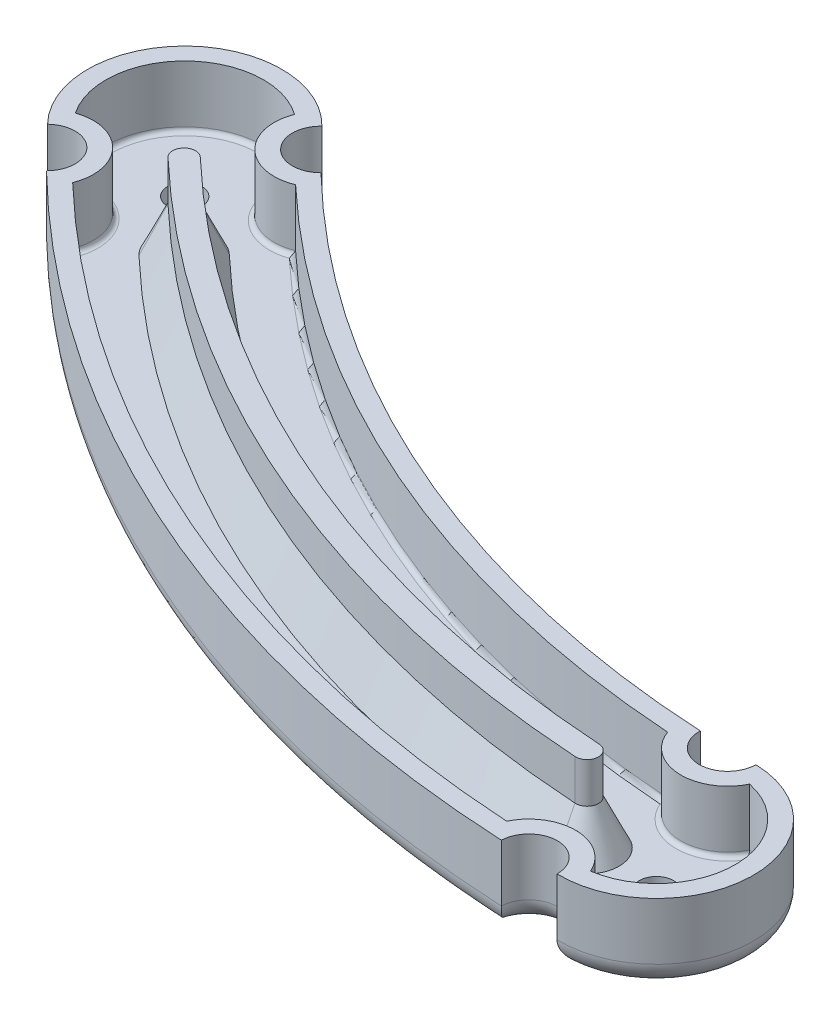
SolidWorks part; units mm, degrees
ref_plane "Front Plane" through (0, 0, 0) normal (0, 0, 1) x (1, 0, 0)
ref_plane "Top Plane" through (0, 0, 0) normal (0, 1, 0) x (1, 0, 0)
ref_plane "Right Plane" through (0, 0, 0) normal (1, 0, 0) x (0, 0, -1)
sketch "Sketch2" plane through (0, 0, 0) normal (0, 1, 0) x (1, 0, 0)
  line L0 (-71.3503, -82.2054) -> (-34958.9124, 35734.8019) construction
  line L1 (-70.1201, -59.1107) -> (-34995.8073, 35720.7213) construction
  line L2 (-39.7979, -107.5277) -> (49945.2079, -1331.9458) construction
  line L3 (31.7139, -92.3079) -> (50015.3873, -1369.9589) construction
  circle A0 centre (0, 0) radius 100 construction
  arc A1 (-0.2082, -108.4975) -> (0.2172, -91.5028) centre (0, -100) ccw
  arc A2 (-67.2386, -62.0626) -> (-79.4101, -73.9309) centre (-73.3212, -68) ccw
  arc A3 (-63.7464, -65.6403) -> (-4.7807, -91.375) centre (0, 0) ccw
  arc A4 (-75.9216, -77.5123) -> (-5.2063, -108.375) centre (0, 0) ccw
  arc A5 (-67.2386, -62.0626) -> (-63.7464, -65.6403) centre (-65.5159, -63.8743) ccw
  arc A6 (-75.9216, -77.5123) -> (-79.4101, -73.9309) centre (-77.6873, -75.7425) ccw
  arc A7 (-4.7807, -91.375) -> (0.2172, -91.5028) centre (-2.2826, -91.4715) ccw
  arc A8 (-0.2082, -108.4975) -> (-5.2063, -108.375) centre (-2.708, -108.4662) ccw
  dimension "D1" = 200
  dimension "D3" = 17
  dimension "D4" = 5
  dimension "D2" = 80
extrude "Boss-Extrude1" add sketch "Sketch2" along normal blind 7
fillet "Fillet1" radius 2 8 edges at (8.4973, 0, 100.2127) (-2.3465, 0, 93.9707) (-36.6, 0, 83.8611) (-67.3049, 0, 65.6206) (-79.2553, 0, 61.9143) (-75.8965, 0, 73.9981) (-43.4, 0, 99.4419) (-2.6467, 0, 105.967)
shell "Shell1" thickness 1.6 removed face at (-37.3691, 7, 85.6233)
sketch "Sketch3" plane through (0, 1.6, 0) normal (0, 1, 0) x (1, 0, 0)
  line L0 (-73.8794, -77.2622) -> (-63.9482, -67.6627) construction
  line L1 (-6.1264, -92.8982) -> (-6.4116, -106.7075) construction
  arc A0 (-68.9138, -72.4625) -> (-6.269, -99.8029) centre (0, 0) ccw construction
  arc A1 (-73.8794, -77.2622) -> (-6.4116, -106.7075) centre (0, 0) ccw construction
  arc A2 (-6.4116, -106.7075) -> (-4.8107, -104.9465) centre (-2.708, -108.4662) ccw construction
  arc A3 (-69.6029, -73.1871) -> (-6.3317, -100.8009) centre (0, 0) ccw
  arc A4 (-68.2246, -71.7378) -> (-6.2063, -98.8048) centre (0, 0) ccw
  arc A5 (-69.6029, -73.1871) -> (-68.2246, -71.7378) centre (-68.9138, -72.4625) cw
  arc A6 (-6.3317, -100.8009) -> (-6.2063, -98.8048) centre (-6.269, -99.8029) ccw
  point P16 (-6.269, -99.8029)
  dimension "D1" = 1
  dimension "D2" = 1
extrude "Boss-Extrude2" add sketch "Sketch3" along normal offset from surface (7.4 mm away) 2 up to face at (-37.4353, 7, 85.775) offset beyond the face yes
chamfer "Chamfer2" distance 1.8 angle 65 4 edges at (-39.5998, 1.6, 90.7346) (-69.6384, 1.6, 71.7733) (-5.271, 1.6, 99.8656) (-40.3998, 1.6, 92.5676) first distance on face at (-37.4529, 1.6, 85.8155)
sketch "Sketch4" plane through (0, 0, 0) normal (0, -1, 0) x (1, 0, 0)
  circle A0 centre (-73.3212, 68) radius 1.5
  circle A1 centre (0, 100) radius 1.5
  dimension "D1" = 3
extrude "Cut-Extrude1" cut sketch "Sketch4" against normal through all
